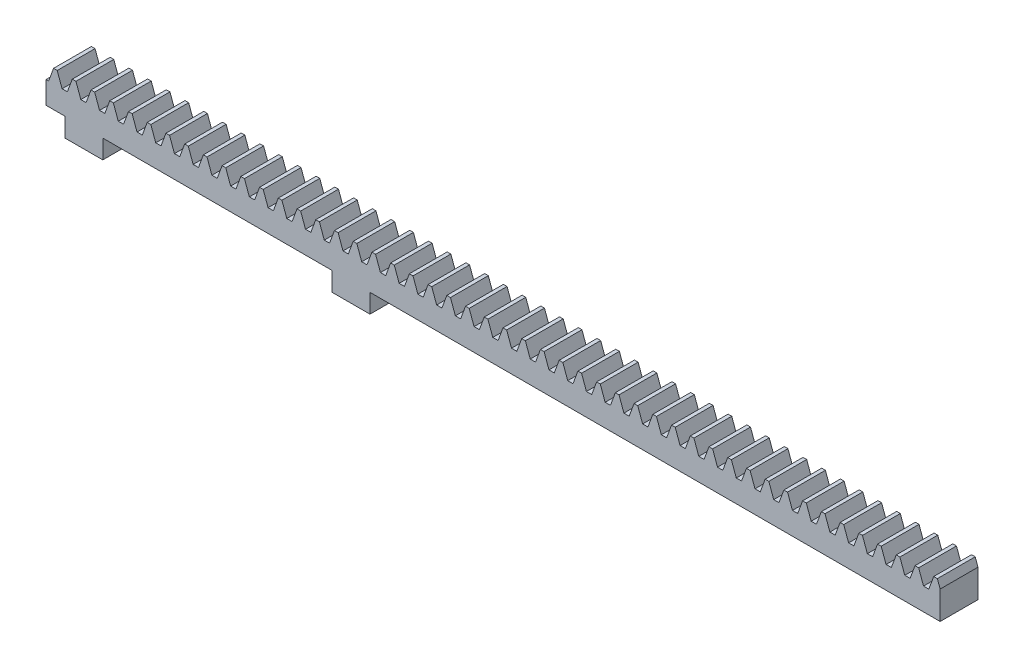
SolidWorks part; units mm, degrees
ref_plane "Plane1" through (0, 0, 0) normal (0, 0, 1) x (1, 0, 0)
ref_plane "Plane2" through (0, 0, 0) normal (0, 1, 0) x (1, 0, 0)
ref_plane "Plane3" through (0, 0, 0) normal (1, 0, 0) x (0, 0, -1)
sketch "HoldingSke" plane through (0, 0, 0) normal (0, 1, 0) x (1, 0, 0)
  line L0 (0, 0) -> (0.1392, 0.9903)
  line L1 (-15, 0) -> (100, 0) construction
  line L2 (0, 0) -> (-2.1039, 2.3779)
  line L3 (0, 0) -> (-11.863, 4.5341)
  line L4 (0, 0) -> (5.6657, 6.5177)
  line L5 (0, 0) -> (-23.7986, -8.8762)
  line L6 (0, 0) -> (-10.5278, -7.1032)
  line L9 (-71.009, 38.7566) -> (69.9449, 90.0596)
  line L10 (-76.2, 3.3779) -> (-71.2, 3.3779)
  line L11 (0, 0) -> (-6.35, 0)
  line L12 (-76.2, 101.6) -> (-76.162, 101.6)
  line L13 (24.9733, 27.94) -> (52.9518, 28.4284)
  line L14 (24.9733, 27.94) -> (24.9743, 27.94)
  line L15 (24.9733, 27.94) -> (100.4006, 29.5858)
  circle A0 centre (0, 0) radius 19.05
  circle A1 centre (0, 0) radius 2.5
  circle A2 centre (0, 0) radius 12.7
  dimension "MPH" = 5
  dimension "Diameter" = 38.1
  dimension "Num_teeth" = 49
  dimension "Pitch" = 1
  dimension "Width" = 6.35
  dimension "Show_teeth" = 998
  dimension "Thickness" = 12.7
  dimension "Ap" = 20
  dimension "Pitch_height" = 5
  dimension "Backlash" = 0.038
  dimension "Addendum_fac" = 1
  dimension "Dedendum_fac" = 1.25
  dimension "Clearance_fac" = 0.25
  dimension "Dedendum_add" = 0.001
  dimension "Length" = 150
  dimension "Module" = 1
sketch "BlankSke" plane through (0, 0, 0) normal (0, 0, 1) x (1, 0, 0)
  line L1 (0, 0) -> (150, 0)
  line L2 (0, 0) -> (0, 6)
  line L3 (0, 6) -> (150, 6)
  line L4 (150, 0) -> (150, 6)
  dimension "Length" = 150
  dimension "Blank_height" = 6
extrude "Blank" add sketch "BlankSke" against normal blind 6.35
sketch "TooCutSkeIll" plane through (0, 0, 0) normal (0, 0, 1) x (1, 0, 0)
  line L0 (-1.2538, 5.9737) -> (-0.5045, 3.9152)
  line L1 (-0.2687, 3.75) -> (0.2687, 3.75)
  line L2 (0.5045, 3.9152) -> (1.2538, 5.9737)
  line L3 (150, 6) -> (0, 6) construction
  line L4 (0, 0) -> (0, 64.897) construction
  line L5 (-13.208, 5) -> (12.954, 5) construction
  line L6 (0, 0) -> (150, 0) construction
  line L7 (0.8994, 5) -> (0.8994, 48.7463) construction
  line L8 (-0.8994, 5) -> (-0.8994, 48.7463) construction
  line L9 (1.2914, 6) -> (1.2914, 6.0254)
  line L10 (-1.2914, 6) -> (-1.2914, 6.0254)
  line L11 (-1.2914, 6.0254) -> (1.2914, 6.0254)
  arc A0 (0.2687, 3.75) -> (0.5045, 3.9152) centre (0.2687, 4.001) ccw
  arc A1 (-0.5045, 3.9152) -> (-0.2687, 3.75) centre (-0.2687, 4.001) ccw
  arc A2 (1.2914, 6) -> (1.2538, 5.9737) centre (1.2914, 5.96) ccw
  arc A3 (-1.2538, 5.9737) -> (-1.2914, 6) centre (-1.2914, 5.96) ccw
  dimension "Root_fillet" = 0.251
  dimension "Break_rad" = 0.04
  dimension "Pitch_height" = 5
  dimension "Gap_width" = 1.7988
  dimension "Dedendum" = 1.25
  dimension "Addendum_plus" = 1.0254
  dimension "Pressure_angle" = 20
extrude "ToothCutIll" [suppressed] cut sketch "TooCutSkeIll" against normal through all
sketch "TooCutSkeSim" plane through (0, 0, 0) normal (0, 0, 1) x (1, 0, 0)
  line L0 (0.4444, 3.75) -> (-0.4444, 3.75)
  line L1 (1.2726, 6.0254) -> (0.4444, 3.75)
  line L2 (0, 17.4625) -> (0, 53.467) construction
  line L3 (1.2726, 6.0254) -> (-1.2726, 6.0254)
  line L6 (-1.2726, 6.0254) -> (-0.4444, 3.75)
  line L9 (-0.8994, 5) -> (0.8994, 5) construction
  line L10 (0, 0) -> (150, 0) construction
  line L11 (0.8994, 5) -> (0.8994, 53.467) construction
  line L12 (-0.8994, 5) -> (-0.8994, 53.467) construction
  dimension "Pitch_height" = 5
  dimension "Pressure_angle" = 20
  dimension "Gap_width" = 1.7988
  dimension "Dedendum" = 1.25
  dimension "Addendum_plus" = 1.0254
extrude "ToothCutSim" cut sketch "TooCutSkeSim" against normal through all
pattern_linear "TeethCuts" count 49 spacing 3.1416 along (1, 0, 0) of "ToothCutIll", "ToothCutSim"
sketch "Sketch1" plane through (0, 0, 0) normal (0, -1, 0) x (1, 0, 0)
  line L0 (48, 0) -> (48, -6.35)
  line L1 (48, 0) -> (54.35, 0)
  line L2 (48, -6.35) -> (54.35, -6.35)
  line L3 (54.35, 0) -> (54.35, -6.35)
  line L6 (0, -6.35) -> (0, 0) construction
  line L7 (0, 0) -> (150, 0) construction
  line L8 (0, -6.35) -> (150, -6.35) construction
  line L9 (3.175, 0) -> (3.175, -6.35)
  line L10 (3.175, 0) -> (9.525, 0)
  line L11 (3.175, -6.35) -> (9.525, -6.35)
  line L12 (9.525, 0) -> (9.525, -6.35)
  dimension "D1" = 48
  dimension "D2" = 6.35
  dimension "D3" = 3.175
  dimension "D4" = 6.35
extrude "ElasticPegs_Extrude" add sketch "Sketch1" along normal blind 3.175
equation "' \"Module@HoldingSke\" = 6.35"
equation "' \"Num_teeth@HoldingSke\" = 12"
equation "' \"Ap@HoldingSke\" =  20"
equation "' \"Width@HoldingSke\" = 0.25 * 25.4"
equation "' \"Show_teeth@HoldingSke\" = 500"
equation "' \"Backlash@HoldingSke\" = 0.009 * 25.4"
equation "' \"Addendum_fac@HoldingSke\" = 1.0"
equation "' \"Dedendum_fac@HoldingSke\" = 1.25"
equation "' \"Dedendum_add@HoldingSke\" = 0.00005 * 25.4"
equation "' \"Clearance_fac@HoldingSke\" = 0.25"
equation "' \"Pitch_height@HoldingSke\" = 1 * 25.4"
equation "' \"Length@HoldingSke\" = 4.71 * 25.4"
equation "\"Pitch@HoldingSke\" = 1 / \"Module@HoldingSke\""
equation "\"MPH@HoldingSke\" = \"Dedendum_fac@HoldingSke\" / \"Pitch@HoldingSke\" + 2 * \"Dedendum_add@HoldingSke\" + 0.002 * 25.4"
equation "\"MPH@HoldingSke\" = ((sgn( \"MPH@HoldingSke\" - \"Pitch_height@HoldingSke\")+1)*( \"MPH@HoldingSke\" - \"Pitch_height@HoldingSke\"))/2 + \"Pitch_height@HoldingSke\""
equation "\"Blank_height@BlankSke\" = \"Pitch_height@HoldingSke\" + \"Addendum_fac@HoldingSke\"  / \"Pitch@HoldingSke\" "
equation "\"Length@BlankSke\" =  \"Length@HoldingSke\""
equation "\"Face_width@Blank\" = \"Width@HoldingSke\""
equation "\"Pressure_angle@TooCutSkeIll\" = \"Ap@HoldingSke\""
equation "\"Addendum_plus@TooCutSkeIll\" =  \"Addendum_fac@HoldingSke\"  / \"Pitch@HoldingSke\" + 0.001 *25.4"
equation "\"Dedendum@TooCutSkeIll\" = \"Dedendum_fac@HoldingSke\"  / \"Pitch@HoldingSke\""
equation "\"Pitch_height@TooCutSkeIll\" =  \"MPH@HoldingSke\""
equation "\"Gap_width@TooCutSkeIll\" = 3.14159265 / 2 / \"Pitch@HoldingSke\" + 6 * \"Backlash@HoldingSke\""
equation "\"Pressure_angle@TooCutSkeSim\" = \"Ap@HoldingSke\""
equation "\"Addendum_plus@TooCutSkeSim\" =  \"Addendum_fac@HoldingSke\"  / \"Pitch@HoldingSke\" + 0.001 * 25.4"
equation "\"Dedendum@TooCutSkeSim\" = \"Dedendum_fac@HoldingSke\"  / \"Pitch@HoldingSke\""
equation "\"Pitch_height@TooCutSkeSim\" =  \"MPH@HoldingSke\""
equation "\"Gap_width@TooCutSkeSim\" = 3.14159265 / 2 / \"Pitch@HoldingSke\" + 6 * \"Backlash@HoldingSke\""
equation "\"Root_fillet@TooCutSkeIll\" = \"Clearance_fac@HoldingSke\" / \"Pitch@HoldingSke\" + \"Dedendum_add@HoldingSke\""
equation "\"Break_rad@TooCutSkeIll\" = 0.02 / \"Pitch@HoldingSke\" * 2"
equation "\"Linear_pitch@TeethCuts\" = 3.14159265 / \"Pitch@HoldingSke\""
equation "\"Num_teeth@HoldingSke\" = int( ( \"Length@HoldingSke\" + 0 ) / (3.14159265 / \"Pitch@HoldingSke\")) + 0.9999  + 1"
equation " \"Num_teeth@TeethCuts\" = int( \"Show_teeth@HoldingSke\" ) + 1"
equation " \"Num_teeth@TeethCuts\" = ((sgn( \"Num_teeth@TeethCuts\" - \"Num_teeth@HoldingSke\" )-1)*( \"Num_teeth@TeethCuts\" - \"Num_teeth@HoldingSke\" ))/-2+ \"Num_teeth@HoldingSke\""
equation " \"Num_teeth@TeethCuts\" = ((sgn( \"Num_teeth@TeethCuts\" - 2.0)+1)*( \"Num_teeth@TeethCuts\" - 2.0))/2 +2.0"
equation "\"CageLeftBottomEdge\"=22.11mm"
equation "\"CageLeftTopEdge\"=22.11mm"
equation "\"CageRightBottomEdge\"=21.63mm"
equation "\"CageRightTopEdge\"=21.63mm"
equation "\"CageHeight\"=86.04mm"
equation "\"CageLength\"=73.76mm"
equation "\"CageTopScrewClearance\"=10mm"
equation "\"CageBottomScrewClearance\"=25mm"
equation "\"CageLeftTopDepth\"= 11.65mm"
equation "\"CageLeftBottomDepth\"=11.11mm"
equation "\"CageLeftTopHeight\"=8.56175mm"
equation "\"CageLeftBottomHeight\"=16mm"
equation "\"CageRightTopDepth\"= 11.05mm"
equation "\"CageRightBottomDepth\"=10.58mm"
equation "\"CageRightTopHeight\"=9.6mm"
equation "\"CageRightBottomHeight\"=15.49mm"
equation "\"CageLeftTopChannelDepth\"=2.41908mm"
equation "\"CageLeftBottomChannelDepth\"=2.588mm"
equation "\"CageLeftChannelHeight\"=11.7mm"
equation "\"CageRightTopChannelDepth\"=2.32mm"
equation "\"CageRightBottomChannelDepth\"=2.318mm"
equation "\"CageRightChannelHeight\"=10mm"
equation "\"CageChanRelHeight\"=23.99mm"
equation "\"CageChanRelDepth\"=5.492mm"
equation "\"CageChamberRadius\"=16.261mm"
equation "\"CageScrewDiameter\"=4.8mm"
equation "\"CageSetScrewDiameter\"=3.5mm"
equation "\"CageAxleRadius\"=6.639mm"
equation "\"CageAxleKeyHeight\"=1.619mm"
equation "\"CageAxleKeyWidth\"=2.662mm"
equation "\"CageHoseWindowWidth\"=16.29mm"
equation "\"CageHoseWindowHeight\"=26.5mm"
equation "\"CageHoseWindow-Edge\"=8.89mm"
equation "\"CageScrew-VerticalEdge\"=5.0mm"
equation "\"CageScrew-HorizontalEdge\"=7.5mm"
equation "\"CageScrew-HoseCornerScrewEdge\"=4.45mm"
equation "\"CageAxle-BottomEdge\"=56.05mm"
equation "\"CageAxle-FrontEdge\"=46.03mm"
equation "\"CageBackSetScrew-Axle\"=40mm"
equation "\"CageFrontSetScrew-Axle\"=22mm"
equation "\"CageVelocityWindow-BackEdge\"=34.8mm"
equation "\"CageVelocityWindow-BottomEdge\"=27.55mm"
equation "\"CageVelocityWindowHeight\"=22.29mm"
equation "\"CageVelocityWindowWidth\"=12.61mm"
equation "\"TriggerSlot-BottomEdge\"=6.35mm"
equation "\"TriggerSlot-FrontEdge\"=15mm"
equation "\"TriggerSlotSize\"=6.7mm"
equation "\"TriggerRackOffset\"=.236224in"
equation "\"TriggerSlotSizeInt\"=.25in"
equation "\"MotorMountLegLength\"=.25in"
equation "\"GearOffset\"=.264907in"
equation "\"TriggerSlotSpacing\"=.25in"
equation "\"TriggerMiniSlotWidth\"=3.5mm"
equation "\"TriggerRackWidth\"=6.5mm"
equation "\"whitemotordepth\"=11.27mm"
equation "\"whitemotorbackdepth\"=3.845mm"
equation "\"whitemotoraxledepth\" = 3.5mm"
equation "\"whitemotoraxleoffset\"=11.4mm"
equation "\"whitemotorwidth\"=12.07mm"
equation "\"whitemotorheight\"=16.68mm"
equation "\"whitemotorcylinderlength\" =13.04mm"
equation "\"whitemotorcylinderradius\"=3.845mm"
equation "\"whitemotorcylinderoffset\"=2.35mm"
equation "\"whitemotorcutoutlength\"=1.88mm"
equation "\"whitemotorouterrad\"=5mm"
equation "\"whitemotorinnerrad\"=2.95mm"
equation "\"elasticracklength\"=2in"
equation "\"elasticrackpegsize\"=.25in"
equation "\"elasticrackpegbuffer\"=.125in"
equation "\"elasticrackpegspacing\"=1.76476378in"
equation "\"elasticbaybuffer\"=.25in"
equation "\"elasticdepth\"=.125in"
equation "\"elasticbaydepth\"=.75in"
equation "\"motormountwidth\"=12mm"
equation "\"motormountcornerfillet\"=3mm"
equation "\"D2@Sketch1\"=\"elasticrackpegsize\""
equation "\"D4@Sketch1\"=\"elasticrackpegsize\""
equation "\"D3@Sketch1\"=\"elasticrackpegsize\"/2"
equation "\"D1@Sketch1\"=\"elasticrackpegspacing\"+\"elasticrackpegsize\"/2"
equation "\"pandiscradius\"=14in"
equation "\"towermaterialwidth\"=.25in"
equation "\"towerslotlength\"=.5in"
equation "\"towermarkerspace\"=5in"
equation "\"towerslothorizoffset\"=1in"
equation "\"towerslothorizspacing\"=2in"
equation "\"towerslotvertoffset\"=3in"
equation "\"towerslotvertspacing\"=1in"
equation "\"towerheight\"=12in"
equation "\"towerupslot\"=1in"
equation "\"toweraxle\"=.5in"
equation "\"stepperouterrad\"=10mm"
equation "\"stepperscrewsize\"=3.45mm"
equation "\"stepperscrewc2c\"=49.5mm"
equation "\"stepperdepthoffset\"=24mm"
equation "\"stepperhorizoffset\"=22.91mm"
equation "\"shaftslotOD\"=18.8mm"
equation "\"shaftslotID\"=13.28mm"
equation "\"shaftkeywidth\"=2.67mm"
equation "\"shaftkeydepth\"=1.8mm"
equation "\"shaftcollartotaldepth\"=12.5mm"
equation "\"shaftsquaredepth\"=6mm"
equation "\"shaftsetscrewsize\"=3.5mm"
equation "\"shaftkeytightdepth\"=1.85mm"
equation "\"shaftslottightID\"=12.78mm"
equation "\"shaftsetscrewoffset\"=9mm"
equation "\"cagecollartotaldepth\"=10mm"
equation "\"cagecollartotalwidth\"=35mm"
equation "\"cagecollarbasedepth\"=4mm"
equation "\"gearhubintdiam\"=30mm"
equation "\"gearhubintwid\"=15mm"
equation "\"towerspeedwidth\"=2in"
equation "\"towerspeedheight\"=8in"
equation "\"towerspeedgap\"=2in"
equation "\"stepperaxleflat\"=.037in"
equation "\"stepperaxlerad\"=0.11811024in"
equation "\"ajaxaxlesize\"=3.87mm"
equation "\"ajaxinnercut\"=2.3mm"
equation "\"ajaxwidth\"=6.1mm"
equation "\"ajaxdiametral\"=25.8854"
equation "\"ajaxcutoutdepth\"=2.3mm"
equation "\"ajax4020gap\"=29.5mm"
equation "\"ajax4010gap\"=24.5mm"
equation "\"ajax20hubbuffer\"=6.1mm"
equation "\"ajax20hubholeoffset\"=.19685in"
equation "\"ajax20hubholesize\"=.059055in"
equation "\"ajax20cutoutint\"=13.4mm"
equation "\"ajax40hubholesize\"=7.21mm"
equation "\"ajax40hubholeoffset\"=10mm"
equation "\"ajax40hubbuffer\"=8.9mm"
equation "\"ajax40cutoutint\"=32.6mm"
equation "\"bearingpandiscrad\"=6.8in"
equation "\"bearingpandiscang\"=48.75deg"
equation "\"bearingclearholedist\"=4.7345in"
equation "\"bearingclearholesize\"=.5in"
equation "\"bearingclearholeang\"=22.5deg"
equation "\"bearingmountholedist\"=4.25in"
equation "\"bearingwirehole\"=1.5in"
equation "\"no6diam\"=.146in"
equation "\"shortconangle\"=20deg"
equation "\"shortconlen\"=.875in"
equation "\"longconlen\"=1.25in"
equation "\"longconangle\"=15deg"
